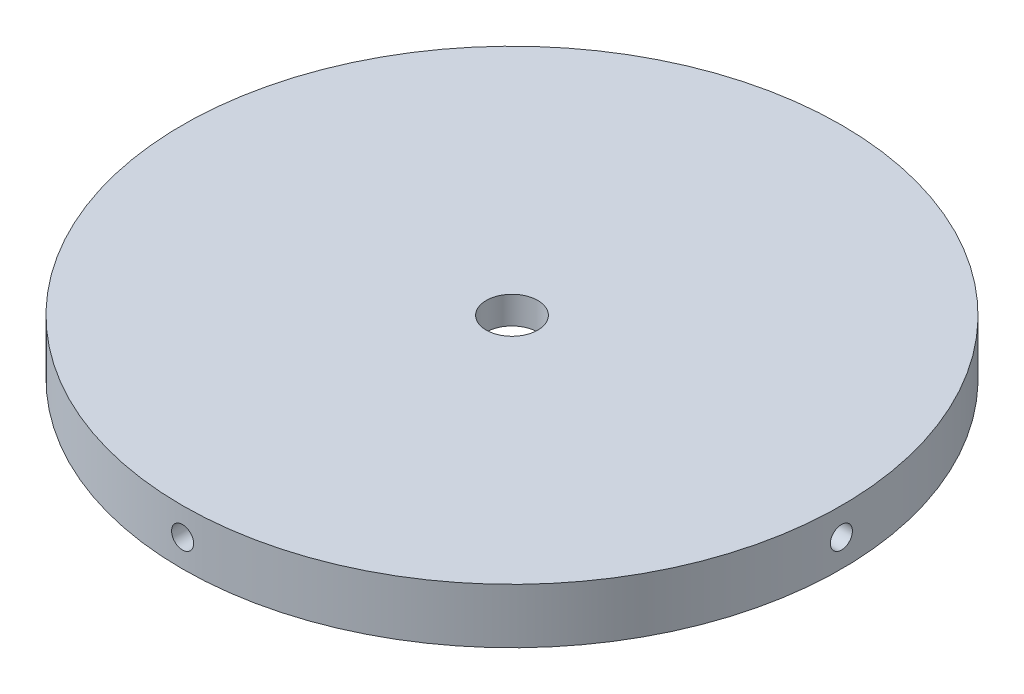
SolidWorks part; units mm, degrees
material "6061-T6 (SS)"
ref_plane "Front Plane" through (0, 0, 0) normal (0, 0, 1) x (1, 0, 0)
ref_plane "Top Plane" through (0, 0, 0) normal (0, 1, 0) x (1, 0, 0)
ref_plane "Right Plane" through (0, 0, 0) normal (1, 0, 0) x (0, 0, -1)
sketch "Sketch2" plane through (0, 0, 0) normal (0, 1, 0) x (1, 0, 0)
  circle A0 centre (0, 0) radius 76.1746
  dimension "D1" = 152.3492
extrude "Boss-Extrude1" add sketch "Sketch2" along normal blind 12.7
sketch "Sketch3" plane through (0, 12.7, 0) normal (0, 1, 0) x (1, 0, 0)
  circle A0 centre (0, 0) radius 5.9531
  dimension "D1" = 11.9062
extrude "Cut-Extrude1" cut sketch "Sketch3" against normal through all both and the other way through all
ref_plane "Plane2" through (0, 6.35, 0) normal (0, 1, 0) x (1, 0, 0)
sketch "Sketch7" plane through (0, 6.35, 0) normal (0, 1, 0) x (1, 0, 0)
  line L0 (-76.1746, 0) -> (76.1746, 0) construction
  line L1 (0, -76.1746) -> (0, 76.1746) construction
  circle A0 centre (0, 0) radius 76.1746 construction
  point P5 (-76.1746, 0)
  point P6 (0, 0)
  point P9 (0, 0)
ref_plane "Plane3" through (-76.1746, 0, 0) normal (1, 0, 0) x (0, 0, -1)
sketch "Sketch9" plane through (-76.1746, 0, 0) normal (1, 0, 0) x (0, 0, -1)
  point P0 (0, 6.35)
hole_wizard "1/4-20 Tapped Hole1" positions "Sketch9" profile "Sketch10" tap size "1/4-20" standard "ANSI Inch"
sketch "Sketch10" plane through (-76.1746, 6.35, 0) normal (0, 1, 0) x (0, 0, 1)
  line L0 (0, 0) -> (0, 26.9338)
  line L1 (0, 26.9338) -> (2.5527, 25.4)
  line L2 (2.5527, 25.4) -> (2.5527, 0)
  line L5 (2.5527, 0) -> (0, 0)
  line L10 (0, 26.9338) -> (-2.5527, 25.4) construction
  line L11 (0, -6.35) -> (0, 107.95) construction
  dimension "Tap Drill Dia." = 5.1054
  dimension "Tap Drill Depth" = 25.4
  dimension "Drill Angle" = 118
cosmetic thread "Hole Thread1" parameters "D1"=12.7, "D2"=6.35
pattern_circular "CirPattern2" count 4 over 270 about axis through (0, 12.7, 0) along (0, -1, 0) of "1/4-20 Tapped Hole1"
sketch "Sketch11" plane through (0, 0, 0) normal (0, -1, 0) x (1, 0, 0)
  circle A0 centre (0, 0) radius 69.8246
  circle A1 centre (0, 0) radius 76.1746 construction
  dimension "D1" = 6.35
extrude "Cut-Extrude2" cut sketch "Sketch11" against normal offset from surface (6.35 mm away) 6.35 up to face at (0, 12.7, 5.9531)
split line "Split Line4"
sketch "Sketch11<2>" plane through (0, 0, 0) normal (0, -1, 0) x (1, 0, 0) same geometry as "Sketch11"
split line "Split Line5"
sketch "Sketch11<3>" plane through (0, 0, 0) normal (0, -1, 0) x (1, 0, 0) same geometry as "Sketch11"
